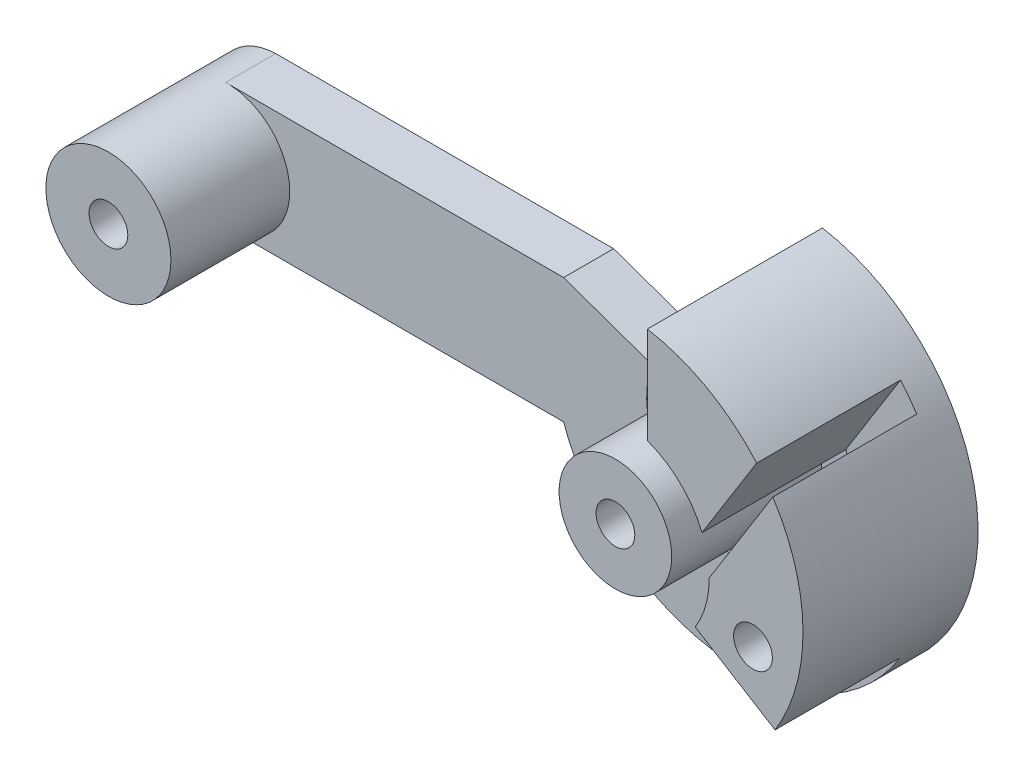
SolidWorks part; units mm, degrees
ref_plane "Plan de face" through (0, 0, 0) normal (0, 0, 1) x (1, 0, 0)
ref_plane "Plan de dessus" through (0, 0, 0) normal (0, 1, 0) x (1, 0, 0)
ref_plane "Plan de droite" through (0, 0, 0) normal (1, 0, 0) x (0, 0, -1)
sketch "Esquisse1" plane through (0, 0, 0) normal (0, 0, 1) x (1, 0, 0)
  line L0 (-0.1213, 4.9985) -> (26.8978, 4.9985)
  line L1 (14.9398, 0) -> (50014.9398, 0) construction
  line L2 (-0.1213, -4.9985) -> (26.8978, -4.9985)
  arc A1 (-0.1213, 4.9985) -> (-0.1213, -4.9985) centre (0, 0) ccw
  arc A3 (26.8978, -4.9985) -> (56.0345, 0.4243) centre (41.0405, 0) ccw
  arc A5 (56.0345, 0.4243) -> (26.8978, 4.9985) centre (41.0405, 0) ccw
  circle A6 centre (0, 0) radius 1.55
  dimension "D1" = 30
  dimension "D2" = 10
  dimension "D3" = 3.1
extrude "Boss.-Extru.1" add sketch "Esquisse1" along normal blind 7 and the other way blind 7
ref_plane "Plan1" through (26.8978, 0, 0) normal (1, 0, 0) x (0, 0, -1)
sketch "Esquisse2" plane through (26.8978, 0, 0) normal (1, 0, 0) x (0, 0, -1)
  line L0 (-7, -4.9985) -> (-6.7498, -4.9985)
  line L1 (-5.2791, -1.7864) -> (-5.4709, -2.5244)
  line L2 (-6.353, -4.2903) -> (-7, -4.2903)
  line L3 (-7, -4.2903) -> (-7, -4.9985)
  arc A0 (-6.7498, -4.9985) -> (-5.2791, -1.7864) centre (-5.1428, -3.7915) cw
  arc A1 (-5.4709, -2.5244) -> (-6.353, -4.2903) centre (-5.1428, -3.7915) ccw
extrude "Boss.-Extru.2" [suppressed] add sketch "Esquisse2" against normal up to vertex
sketch "Esquisse3" plane through (0, 0, 7) normal (0, 0, 1) x (1, 0, 0)
  circle A0 centre (41.0405, 0) radius 4.5
  circle A1 centre (41.0405, 0) radius 7.5
  dimension "D1" = 15
  dimension "D2" = 9
extrude "Enlèv. mat.-Extru.1" cut sketch "Esquisse3" against normal blind 12
sketch "Esquisse4" plane through (0, 0, 7) normal (0, 0, 1) x (1, 0, 0)
  line L0 (26.8978, 4.9985) -> (33.9691, 2.4993)
  line L1 (41.0405, 0) -> (26.8978, 4.9985) construction
  line L3 (43.5945, 14.781) -> (43.5945, 7.0517)
  circle A0 centre (41.0405, 0) radius 7.5 construction
  circle A1 centre (41.0405, 0) radius 7.5 construction
  arc A2 (26.8978, -4.9985) -> (26.8978, 4.9985) centre (41.0405, 0) ccw construction
  arc A3 (26.8978, 4.9985) -> (43.5945, 14.781) centre (41.0405, 0) cw
  arc A4 (33.9691, 2.4993) -> (43.5945, 7.0517) centre (41.0405, 0) cw
extrude "Enlèv. mat.-Extru.2" cut sketch "Esquisse4" against normal up to surface (14 mm away) up to face at (1.55, 0, -7)
sketch "Esquisse5" plane through (0, 0, 7) normal (0, 0, 1) x (1, 0, 0)
  circle A0 centre (41.0405, 0) radius 1.55
  dimension "D1" = 3.1
extrude "Enlèv. mat.-Extru.3" cut sketch "Esquisse5" against normal up to surface (14 mm away) up to face at (1.55, 0, -7)
sketch "Esquisse6" plane through (0, 0, 7) normal (0, 0, -1) x (-1, 0, 0)
  line L0 (-52.3375, 9.868) -> (-47.9676, 2.8748)
  line L2 (-48.5224, 0.0173) -> (-50048.5224, 0.0173) construction
  line L6 (-48.5404, 0.0173) -> (-53.6277, 8.1586)
  arc A0 (-43.5945, 14.781) -> (-26.8978, -4.9985) centre (-41.0405, 0) ccw construction
  arc A1 (-52.3375, 9.868) -> (-53.6277, 8.1586) centre (-41.0405, 0) ccw
  arc A2 (-47.9676, 2.8748) -> (-48.5404, 0.0173) centre (-41.0405, 0) ccw
  circle A3 centre (-41.0405, 0) radius 7.5 construction
  arc A4 (-33.9691, 2.4993) -> (-43.5945, 7.0517) centre (-41.0405, 0) ccw construction
  arc A5 (-43.5945, 14.781) -> (-26.8978, -4.9985) centre (-41.0405, 0) ccw construction
  point P9 (-48.5391, -0.1422)
  dimension "D1" = 58
  dimension "D2" = 2
extrude "Enlèv. mat.-Extru.4" cut sketch "Esquisse6" along normal blind 11.5 contours L0 A2 A1 region at (50.6741, 5.2717, 7)
sketch "Esquisse7" plane through (0, 0, 7) normal (0, 0, 1) x (1, 0, 0)
  line L1 (47.423, -3.9386) -> (53.8056, -7.8772)
  line L2 (33.9691, 2.4993) -> (26.8978, 4.9985)
  line L3 (26.8978, 4.9985) -> (-0.1213, 4.9985)
  line L4 (-0.1213, -4.9985) -> (26.8978, -4.9985)
  line L5 (41.0405, 0) -> (53.8056, -7.8772) construction
  circle A0 centre (41.0405, 0) radius 7.5 construction
  arc A1 (33.9691, 2.4993) -> (47.423, -3.9386) centre (41.0405, 0) ccw
  arc A2 (-0.1213, 4.9985) -> (-0.1213, -4.9985) centre (-0.2426, 0) ccw
  arc A3 (26.8978, -4.9985) -> (53.8056, -7.8772) centre (41.0405, 0) ccw
  arc A4 (26.8978, -4.9985) -> (53.6277, 8.1586) centre (41.0405, 0) ccw construction
extrude "Enlèv. mat.-Extru.5" cut sketch "Esquisse7" against normal blind 10
sketch "Esquisse8" plane through (0, 0, -3) normal (0, 0, 1) x (1, 0, 0)
  circle A0 centre (0, 0) radius 1.55
  circle A1 centre (0, 0) radius 5
  arc A2 (-0.1213, 4.9985) -> (-0.1213, -4.9985) centre (0, 0) ccw construction
  circle A3 centre (0, 0) radius 1.55 construction
extrude "Boss.-Extru.3" add sketch "Esquisse8" along normal blind 9.5
sketch "Sketch1" plane through (0, 0, 7) normal (0, 0, 1) x (1, 0, 0)
  line L0 (52.0405, -3) -> (41.0405, -3) construction
  line L1 (41.0405, 0) -> (41.0405, -3) construction
  circle A0 centre (52.0405, -3) radius 1.55
  dimension "D3" = 3.1
  dimension "D1" = 3
  dimension "D2" = 11
extrude "Cut-Extrude1" cut sketch "Sketch1" against normal up to surface (14 mm away) up to face at (42.5905, 0, -7)
